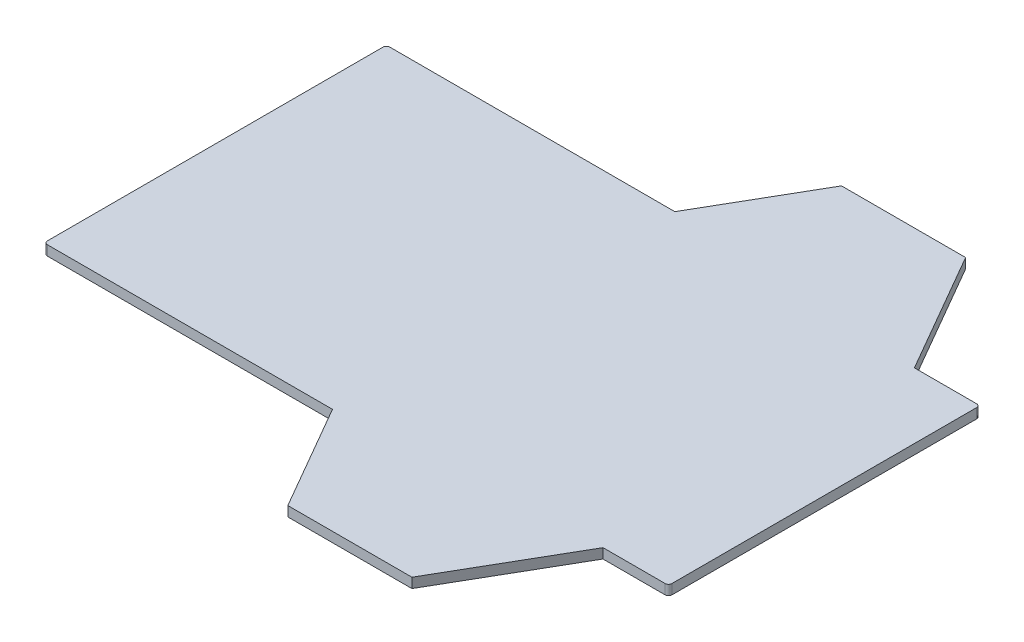
SolidWorks part; units mm, degrees
material "Acrylic (Medium-high impact)"
ref_plane "Front Plane" through (0, 0, 0) normal (0, 0, 1) x (1, 0, 0)
ref_plane "Top Plane" through (0, 0, 0) normal (0, 1, 0) x (1, 0, 0)
ref_plane "Right Plane" through (0, 0, 0) normal (1, 0, 0) x (0, 0, -1)
sketch "Sketch1" plane through (0, 0, 0) normal (0, 1, 0) x (1, 0, 0)
  line L0 (0, 52) -> (0, -52)
  line L12 (0, 52) -> (87.6171, 52)
  line L13 (87.6171, 52) -> (106.15, 84.1)
  line L14 (106.15, 84.1) -> (143.85, 84.1)
  line L15 (143.85, 84.1) -> (165.0965, 47.3)
  line L16 (165.0965, 47.3) -> (185, 47.3)
  line L17 (185, 47.3) -> (185, -47.3)
  line L18 (185, -47.3) -> (165.0965, -47.3)
  line L19 (165.0965, -47.3) -> (143.85, -84.1)
  line L20 (143.85, -84.1) -> (106.15, -84.1)
  line L21 (106.15, -84.1) -> (87.6171, -52)
  line L22 (87.6171, -52) -> (0, -52)
  line L23 (125, 84.1) -> (125, -84.1) construction
  point P12 (125, 0)
  point P15 (0, 0)
  point P23 (185, 0)
  dimension "D1" = 104
  dimension "D2" = 37.7
  dimension "D3" = 32.1
  dimension "D4" = 120
  dimension "D5" = 143.85
  dimension "D6" = 185
  dimension "D7" = 94.6
extrude "Boss-Extrude1" add sketch "Sketch1" along normal blind 3
fillet "Fillet1" radius 1 4 edges at (0, 1.5, 52) (0, 1.5, -52) (185, 1.5, -47.3) (185, 1.5, 47.3)
